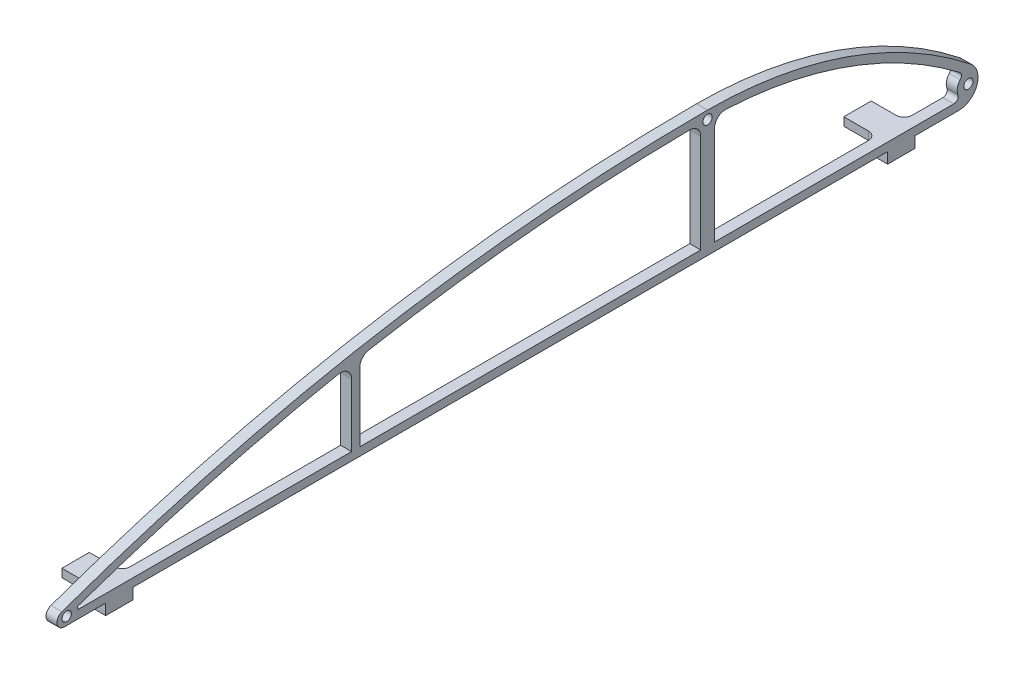
SolidWorks part; units mm, degrees
other "Marquage1"
sketch "Esquisse8" plane through (8, 0, -172.8424) normal (1, 0, 0) x (0, 0, -1)
other "Marquage2"
sketch "Esquisse10" plane through (-6, 20, -172.8424) normal (-0.8365, 0.2588, -0.483) x (-0.5, 0, 0.866)
other "Marquage3"
sketch "Esquisse11" plane through (0, 0, 0) normal (-0.0501, -0.1345, 0.9896) x (0.9942, 0.0873, 0.0622)
ref_plane "Plan de face" through (0, 0, 0) normal (0, 0, 1) x (1, 0, 0)
ref_plane "Plan de dessus" through (0, 0, 0) normal (0, 1, 0) x (1, 0, 0)
ref_plane "Plan de droite" through (0, 0, 0) normal (1, 0, 0) x (0, 0, -1)
sketch "Esquisse2" plane through (0, 0, 0) normal (1, 0, 0) x (0, 0, -1)
  line L0 (0, 0) -> (170.8732, 0)
  arc A1 (173.0499, 6.2408) -> (125, 23) centre (125, -54.2609) ccw
  arc A3 (170.8732, 0) -> (173.0499, 6.2408) centre (170.8732, 3.5) ccw
  arc A4 (125, 23) -> (0, 0) centre (125, -328.1739) ccw
  point P10 (180, 0)
  dimension "D1" = 180
  dimension "D2" = 3.5
  dimension "D3" = 23
  dimension "D4" = 55
extrude "Boss.-Extru.1" add sketch "Esquisse2" along normal blind 2
sketch "Esquisse4" plane through (2, 0, 0) normal (1, 0, 0) x (0, 0, -1)
  line L0 (8, 0) -> (8, 2.9365) construction
  line L1 (0, 0) -> (8, 1.4683) construction
  line L10 (174.369, 3.3283) -> (172.619, 3.3283) construction
  line L11 (0, 0) -> (170.8732, 0) construction
  circle A6 centre (125, 21.5) radius 0.85
  circle A12 centre (172.619, 3.3283) radius 0.85
  arc A13 (170.8732, 0) -> (173.0499, 6.2408) centre (170.8732, 3.5) ccw construction
  circle A15 centre (8, 1.4683) radius 0.85
  arc A16 (125, 23) -> (0, 0) centre (125, -328.1739) ccw construction
  dimension "D1" = 1.7
  dimension "D2" = 1.7
  dimension "D7" = 1.7
  dimension "D3" = 1.5
  dimension "D4" = 8
  dimension "D6" = 1.75
extrude "Enlèv. mat.-Extru.2" cut sketch "Esquisse4" against normal through all
sketch "Esquisse9" plane through (0, 0, 0) normal (1, 0, 0) x (0, 0, -1)
  line L26 (126.25, 1.5) -> (171.6918, 1.5)
  line L35 (8.4369, 1.5) -> (170.8732, 1.5)
  line L36 (10.0498, 1.5) -> (60, 1.5)
  line L40 (61.5, 1.5) -> (123.75, 1.5)
  line L42 (60, 1.5) -> (60, 15.4055)
  line L44 (61.5, 1.5) -> (61.5, 15.6859)
  line L45 (123.75, 21.4978) -> (123.75, 1.5)
  line L46 (126.25, 21.4978) -> (126.25, 1.5)
  arc A20 (60, 15.4055) -> (9.9693, 2.0378) centre (125, -328.1739) ccw
  circle A21 centre (125, 21.5) radius 0.85 construction
  circle A22 centre (8, 1.4683) radius 0.85 construction
  arc A23 (173.0499, 6.2408) -> (125, 23) centre (125, -54.2609) ccw construction
  arc A25 (171.9, 5.2481) -> (171.6918, 1.5) centre (172.619, 3.3283) ccw
  circle A26 centre (172.619, 3.3283) radius 0.85 construction
  arc A35 (170.8732, 1.5) -> (172.117, 5.0662) centre (170.8732, 3.5) ccw
  arc A39 (172.117, 5.0662) -> (125, 21.5) centre (125, -54.2609) ccw
  arc A40 (125, 21.5) -> (8.4369, 1.5) centre (125, -328.1739) ccw
  arc A42 (171.9, 5.2481) -> (126.25, 21.4978) centre (125, -54.2609) ccw
  arc A43 (123.75, 21.4978) -> (61.5, 15.6859) centre (125, -328.1739) ccw
  arc A54 (10.0498, 1.5) -> (9.9693, 2.0378) centre (8, 1.4683) ccw
  dimension "D1" = 1.5
  dimension "D2" = 1.25
  dimension "D3" = 1.2
  dimension "D5" = 1.25
  dimension "D4" = 1.2
  dimension "D6" = 1.5
  dimension "D7" = 60
extrude "Enlèv. mat.-Extru.3" cut sketch "Esquisse9" along normal blind 4
fillet "Congé2" radius 1.35 1 edges at (1, 0, 0)
sketch "Esquisse12" plane through (0, 0, 0) normal (0, -1, 0) x (1, 0, 0)
  line L0 (0, -162.8732) -> (2, -162.8732)
  line L1 (0, -7.5659) -> (0, -170.8732) construction
  line L2 (2, -7.5659) -> (2, -170.8732) construction
  line L3 (2, -170.8732) -> (0, -170.8732) construction
  line L4 (0, -157.8732) -> (2, -157.8732)
  line L5 (0, -20.1127) -> (2, -20.1127)
  line L6 (0, -15.1127) -> (2, -15.1127)
  line L7 (0, -7.1127) -> (2, -7.1127) construction
  line M5 (2, -170.8732) -> (2, -7.5659)
  line M7 (0, -7.5659) -> (0, -170.8732)
  dimension "D1" = 8
  dimension "D2" = 5
  dimension "D3" = 8
  dimension "D4" = 5
extrude "Boss.-Extru.2" add sketch "Esquisse12" along normal blind 2 contours L4 L0 M7 M5 | L6 L5 M7 M5 region at (1, 0, -160.3732) region at (1, 0, -17.6127)
fillet "Congé3" radius 2 4 edges at (1, 21.4978, -126.25) (1, 21.4978, -123.75) (1, 15.4055, -60) (1, 15.6859, -61.5)
fillet "Congé4" radius 0.8 2 edges at (1, 1.5, -171.6918) (1, 5.2481, -171.9)
sketch "Esquisse13" plane through (0, 0, 0) normal (-1, 0, 0) x (0, 0, 1)
  line L1 (-157.8732, -2) -> (-157.8732, 0) construction
  line L2 (-162.8732, 0) -> (-157.8732, 0)
  line L3 (-162.8732, 0) -> (-162.8732, 1.5)
  line L4 (-162.8732, 1.5) -> (-157.8732, 1.5)
  line L5 (-157.8732, 0) -> (-157.8732, 1.5)
  line L6 (-126.25, 1.5) -> (-169.9609, 1.5) construction
  line L7 (-15.1127, -2) -> (-15.1127, 0) construction
  line L8 (-20.1127, 0) -> (-15.1127, 0)
  line L9 (-20.1127, 0) -> (-20.1127, 1.5)
  line L10 (-20.1127, 1.5) -> (-15.1127, 1.5)
  line L11 (-15.1127, 0) -> (-15.1127, 1.5)
  line L12 (-10.0498, 1.5) -> (-60, 1.5) construction
extrude "Boss.-Extru.3" add sketch "Esquisse13" along normal blind 6
fillet "Congé5" radius 1.5 4 edges at (0, 0.75, -15.1127) (0, 0.75, -20.1127) (0, 0.75, -162.8732) (0, 0.75, -157.8732)
